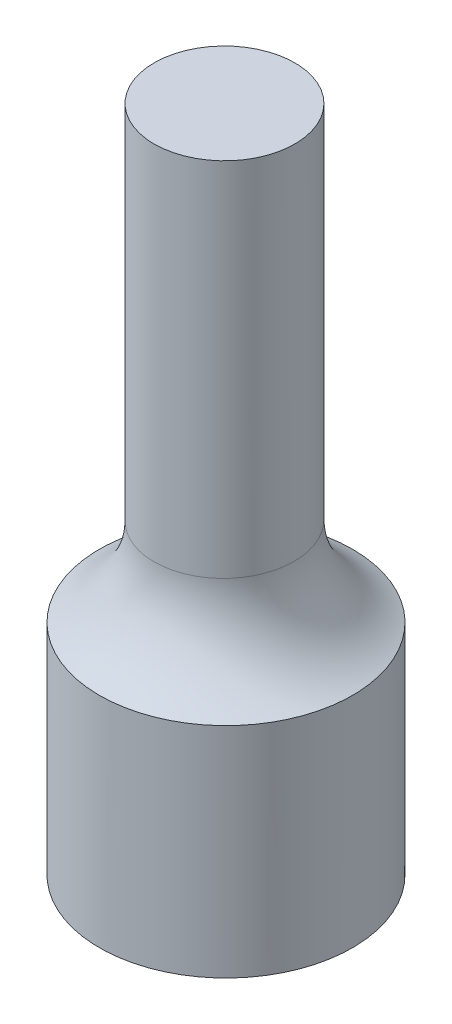
SolidWorks part; units mm, degrees
ref_plane "Front Plane" through (0, 0, 0) normal (0, 0, 1) x (1, 0, 0)
ref_plane "Top Plane" through (0, 0, 0) normal (0, 1, 0) x (1, 0, 0)
ref_plane "Right Plane" through (0, 0, 0) normal (1, 0, 0) x (0, 0, -1)
sketch "Sketch1" plane through (0, 0, 0) normal (0, 1, 0) x (1, 0, 0)
  line L0 (4.55, 9.1) -> (4.55, 0) construction
  line L1 (0, 0) -> (9.1, 0)
  line L2 (0, 0) -> (0, 9.1)
  line L3 (0, 9.1) -> (9.1, 9.1)
  line L4 (9.1, 0) -> (9.1, 9.1)
  circle A0 centre (4.55, 4.55) radius 9
  dimension "D2" = 18
  dimension "D1" = 9.1
extrude "Boss-Extrude1" add sketch "Sketch1" along normal blind 13 contours A0 | L2 L1 L4 L3
sketch "Sketch2" plane through (0, 13, 0) normal (0, 1, 0) x (1, 0, 0)
  line L0 (4.55, 13.55) -> (4.55, -4.45) construction
  circle A0 centre (4.55, 4.55) radius 9 construction
  circle A1 centre (4.55, 4.55) radius 9
  dimension "D1" = 18
extrude "Boss-Extrude2" add sketch "Sketch2" along normal blind 2.54
sketch "Sketch3" plane through (0, 15.54, 0) normal (0, 1, 0) x (1, 0, 0)
  line L0 (4.55, 13.55) -> (4.55, -4.45) construction
  circle A0 centre (4.55, 4.55) radius 9 construction
  circle A1 centre (4.55, 4.4431) radius 5
  dimension "D1" = 10
extrude "Boss-Extrude3" add sketch "Sketch3" along normal blind 32
fillet "Fillet2" radius 7 1 edges at (4.55, 15.54, 0.5569)
